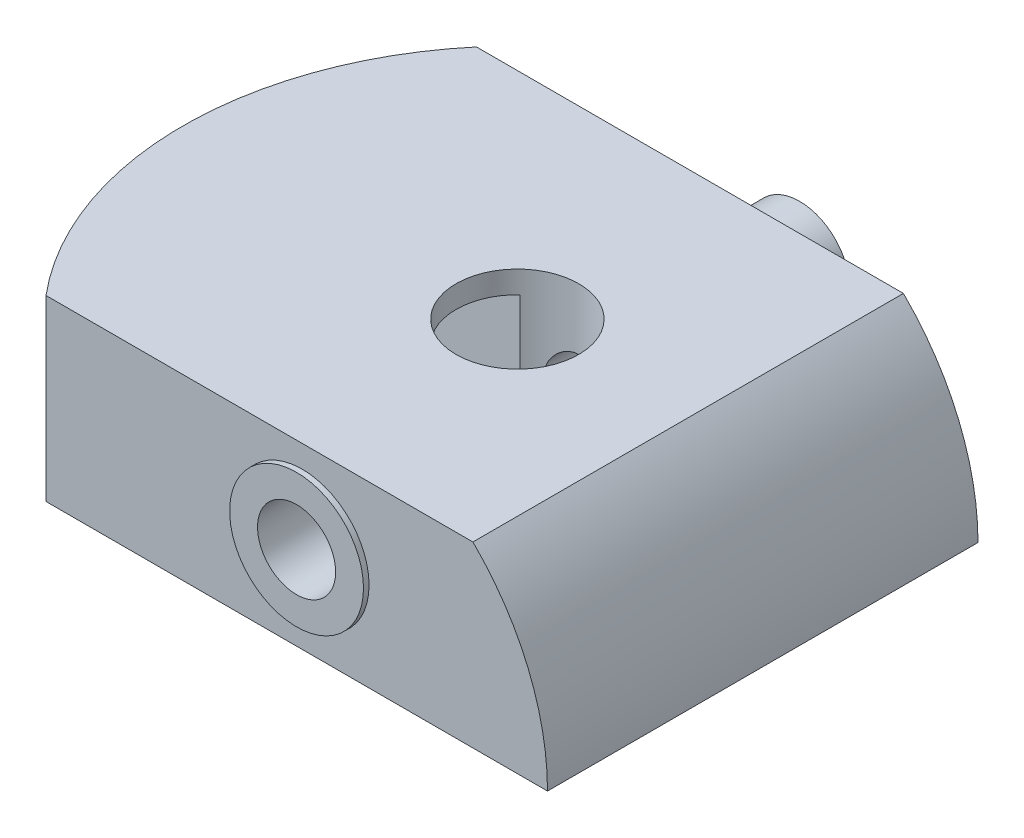
SolidWorks part; units mm, degrees
ref_plane "Front Plane" through (0, 0, 0) normal (0, 0, 1) x (1, 0, 0)
ref_plane "Top Plane" through (0, 0, 0) normal (0, 1, 0) x (1, 0, 0)
ref_plane "Right Plane" through (0, 0, 0) normal (1, 0, 0) x (0, 0, -1)
sketch "Sketch1" plane through (0, 0, 0) normal (0, 0, 1) x (1, 0, 0)
  line L0 (18.3902, 0) -> (18.3902, -4) construction
  line L1 (1.3902, -4) -> (1.3902, 4)
  line L2 (1.3902, -4) -> (18.3902, -4)
  line L3 (1.3902, 4) -> (29.3902, 4)
  line L4 (29.3902, 4) -> (29.3902, -4)
  line L5 (18.3902, 0) -> (18.3902, 4) construction
  line L6 (18.3902, -4) -> (29.3902, -4)
extrude "Boss-Extrude1" add sketch "Sketch1" along normal blind 19.3 contours L3 L1 region at (15.3902, 0, 0)
sketch "Sketch5" plane through (0, 0, 0) normal (0, 1, 0) x (1, 0, 0)
  line L0 (18.3902, -9.65) -> (8.8902, -9.65) construction
  line L1 (18.3902, -9.65) -> (25.3902, -9.65) construction
  line L2 (18.3902, -9.65) -> (18.3902, -4.15) construction
  line L3 (18.3902, -9.65) -> (18.3902, -15.15) construction
  line L4 (25.3902, -9.65) -> (25.3902, -8.15)
  line L5 (25.3902, -8.15) -> (23.8902, -8.15)
  line L6 (23.8902, -8.15) -> (22.3902, -8.15) construction
  line L7 (22.3902, -8.15) -> (22.3902, -5.15) construction
  line L8 (23.8902, -8.15) -> (22.3902, -5.15)
  line L9 (22.3902, -5.15) -> (22.3902, -4.15)
  line L10 (22.3902, -4.15) -> (18.3902, -4.15)
  line L11 (18.3902, -4.15) -> (14.1402, -4.15)
  line L12 (14.1402, -4.15) -> (14.1402, -5.15)
  line L13 (8.8902, -9.65) -> (8.8902, -14.15) construction
  line L14 (14.1402, -5.15) -> (8.8902, -5.15)
  line L15 (25.3902, -9.65) -> (25.3902, -11.15)
  line L16 (25.3902, -11.15) -> (23.8902, -11.15)
  line L17 (23.8902, -11.15) -> (22.3902, -11.15) construction
  line L18 (22.3902, -11.15) -> (22.3902, -14.15) construction
  line L19 (23.8902, -11.15) -> (22.3902, -14.15)
  line L20 (22.3902, -14.15) -> (22.3902, -15.15)
  line L21 (22.3902, -15.15) -> (18.3902, -15.15)
  line L22 (18.3902, -15.15) -> (14.1402, -15.15)
  line L23 (14.1402, -15.15) -> (14.1402, -14.15)
  line L24 (8.8902, -9.65) -> (8.8902, -5.15) construction
  line L25 (8.8902, -14.15) -> (1.3902, -14.15)
  line L27 (14.1402, -14.15) -> (8.8902, -14.15)
  line L28 (1.3902, -14.15) -> (1.3902, -9.15)
  line L29 (1.3902, -9.15) -> (1.3902, -5.15)
  line L31 (1.3902, -5.15) -> (8.8902, -5.15)
  line L32 (23.8902, -11.15) -> (23.8902, -8.15)
extrude "Pot Insert" cut sketch "Sketch5" along normal blind 2.5 from offset 4 contours L19 L32 L8 L9 L10 L11 L12 L14 L31 L29 L28 L25 L27 L23 L22 L21 L20 region at (12.8474, 0, 9.65) offset against normal yes
sketch "Sketch6" plane through (0, 0, 0) normal (0, 1, 0) x (1, 0, 0)
  circle A0 centre (18.3902, -9.65) radius 2.75
extrude "Pot Hole" cut sketch "Sketch6" against normal through all from offset 4
sketch "Sketch8" plane through (0, 0, 0) normal (0, 0, 1) x (1, 0, 0)
  line L0 (1.3902, 0) -> (18.3902, 0) construction
  line L3 (1.3902, -4) -> (1.3902, 4) construction
  circle A0 centre (18.3902, 0) radius 2.25
extrude "Boss-Extrude2" add sketch "Sketch8" against normal blind 3
sketch "Sketch18" plane through (0, 0, 0) normal (0, 0, 1) x (1, 0, 0)
  circle A0 centre (18.3902, 0) radius 3
extrude "Boss-Extrude4" add sketch "Sketch18" along normal blind 0.25 from offset 19.3
sketch "Sketch17" plane through (0, 0, 0) normal (0, 0, 1) x (1, 0, 0)
  circle A0 centre (18.3902, 0) radius 3
extrude "Boss-Extrude3" add sketch "Sketch17" against normal blind 0.25
sketch "Sketch7" plane through (0, 0, 0) normal (0, 1, 0) x (1, 0, 0)
  line L0 (18.3902, -24.65) -> (1.3902, -24.65)
  line L1 (1.3902, -24.65) -> (1.3902, 5.35)
  line L2 (1.3902, 5.35) -> (18.3902, 5.35)
  circle A1 centre (18.3902, -9.65) radius 15
extrude "Abduction Curve" cut sketch "Sketch7" against normal through all from offset 4 contours A1 | A1 region at (9.8902, 0, 24.3052)
sketch "Sketch13" plane through (0, 0, 0) normal (0, 0, 1) x (1, 0, 0)
  circle A0 centre (18.3902, 0) radius 1.75
extrude "Abduction Cable Hole" cut sketch "Sketch13" along normal blind 9 from offset 11
sketch "Sketch14" plane through (0, 0, 0) normal (0, 0, 1) x (1, 0, 0)
  line L0 (6.9064, -4) -> (29.3902, -4) construction
  line L1 (18.1483, 7.2419) -> (29.3902, 7.2419)
  line L2 (29.3902, 7.2419) -> (29.3902, -4)
  circle A0 centre (18.1483, -4) radius 11.2419
extrude "Flex-Extend Curve" cut sketch "Sketch14" along normal through all contours A0 | A0 region at (26.8792, 4.7308, 0)
sketch "Sketch15" plane through (0, 0, 0) normal (0, 1, 0) x (1, 0, 0)
  line L1 (18.3902, -11.65) -> (9.3902, -11.65)
  line L2 (9.3902, -11.65) -> (9.3902, -7.65)
  line L3 (9.3902, -7.65) -> (18.3902, -7.65)
  line L4 (18.3902, -7.65) -> (18.3902, -11.65)
extrude "Cut-Extrude1" cut sketch "Sketch15" along normal blind 4.5 from offset 1.5 offset against normal yes
sketch "Sketch16" plane through (0, 0, -3) normal (0, 0, -1) x (-1, 0, 0)
  circle A0 centre (-18.3902, 0) radius 1.25
extrude "Cut-Extrude2" cut sketch "Sketch16" against normal through all
